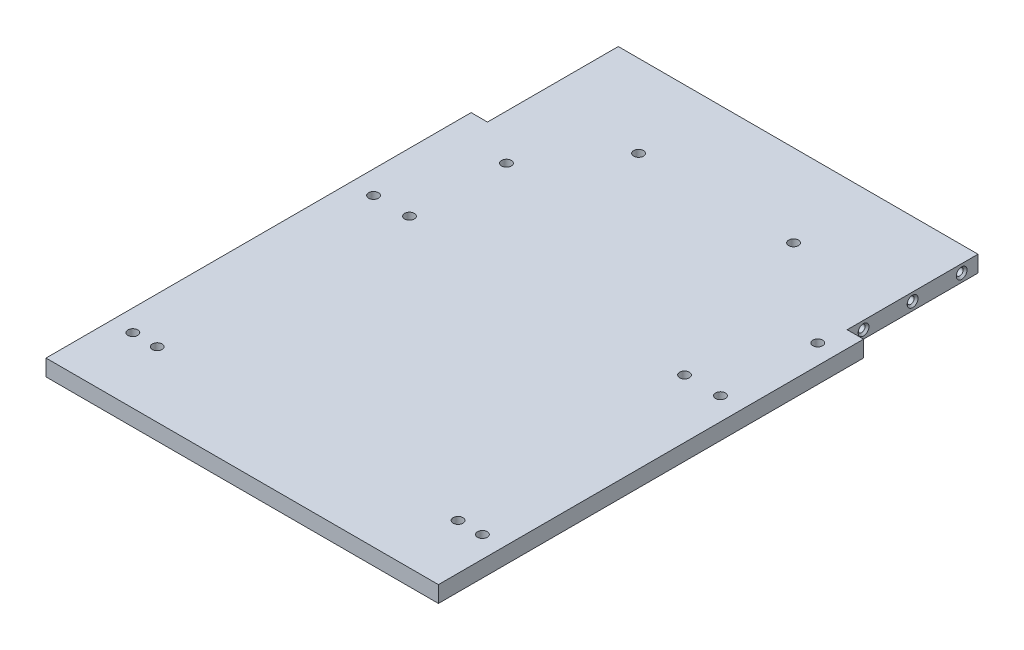
SolidWorks part; units mm, degrees
ref_plane "Front Plane" through (0, 0, 0) normal (0, 0, 1) x (1, 0, 0)
ref_plane "Top Plane" through (0, 0, 0) normal (0, 1, 0) x (1, 0, 0)
ref_plane "Right Plane" through (0, 0, 0) normal (1, 0, 0) x (0, 0, -1)
sketch "Sketch1" plane through (0, 0, 0) normal (0, 1, 0) x (1, 0, 0)
  line L0 (-6.35, 0) -> (-6.35, -50.8)
  line L1 (-6.35, 0) -> (-146.05, 0)
  line L2 (0, -50.8) -> (0, -215.9)
  line L3 (0, -215.9) -> (-152.4, -215.9)
  line L4 (-152.4, -50.8) -> (-152.4, -215.9)
  line L5 (-6.35, -50.8) -> (0, -50.8)
  line L6 (-146.05, 0) -> (-146.05, -50.8)
  line L7 (-146.05, -50.8) -> (-152.4, -50.8)
  point P7 (-3.175, -50.8)
  dimension "D1" = 152.4
  dimension "D2" = 215.9
  dimension "D3" = 50.8
  dimension "D4" = 6.35
  dimension "D5" = 6.35
  dimension "D6" = 50.8
extrude "Boss-Extrude1" add sketch "Sketch1" along normal blind 6.35
sketch "Sketch2" plane through (-6.35, 0, 0) normal (1, 0, 0) x (0, 0, -1)
  line L0 (-50.8, 6.35) -> (-50.8, 0) construction
  line L1 (-50.8, 6.35) -> (-50.8, 0) construction
  line L2 (-50.8, 0) -> (0, 0) construction
  circle A0 centre (-44.45, 3.175) radius 1.8288
  circle A1 centre (-25.4, 3.175) radius 1.8288
  circle A2 centre (-6.35, 3.175) radius 1.8288
  dimension "D4" = 3.175
  dimension "D5" = 3.175
  dimension "D6" = 3.6576
  dimension "D7" = 3.6576
  dimension "D8" = 3.6576
  dimension "D1" = 6.35
  dimension "D2" = 25.4
  dimension "D3" = 44.45
hole_wizard "#6-32 Tapped Hole1" positions "Sketch3" profile "Sketch4" tap size "#6-32" standard "ANSI Inch"
sketch "Sketch3" plane through (-6.35, 0, 0) normal (1, 0, 0) x (0, 0, -1)
  point P0 (-44.45, 3.175)
  point P3 (-25.4, 3.175)
  point P6 (-6.35, 3.175)
sketch "Sketch4" plane through (-6.35, 3.175, 44.45) normal (0, 1, 0) x (0, 0, -1)
  line L0 (0, 0) -> (0, 12.7)
  line L1 (0, 12.7) -> (1.3525, 11.8873)
  line L2 (1.3525, 11.8873) -> (1.3525, 0.748)
  line L3 (1.3525, 0.748) -> (2.1006, 0)
  line L5 (2.1006, 0) -> (0, 0)
  line L6 (-1.3525, 0.748) -> (-2.1006, 0) construction
  line L10 (0, 12.7) -> (-1.3526, 11.8873) construction
  line L11 (0, -6.35) -> (0, 107.95) construction
  dimension "Tap Drill Dia." = 2.7051
  dimension "Tap Drill Depth" = 12.7
  dimension "Near C'Sink Dia." = 4.2012
  dimension "Near C'Sink Angle" = 90
  dimension "Drill Angle" = 118
cosmetic thread "Hole Thread13" parameters "D1"=10.16, "D2"=3.5052
cosmetic thread "Hole Thread14" parameters "D1"=10.16, "D2"=3.5052
cosmetic thread "Hole Thread15" parameters "D1"=10.16, "D2"=3.5052
sketch "Sketch5" plane through (-146.05, 0, 0) normal (-1, 0, 0) x (0, 0, 1)
  circle A0 centre (6.35, 3.175) radius 1.8288
  circle A1 centre (25.4, 3.175) radius 1.8288
  circle A2 centre (44.45, 3.175) radius 1.8288
  dimension "D1" = 3.6576
  dimension "D2" = 3.6576
  dimension "D3" = 3.6576
hole_wizard "#6-32 Tapped Hole2" positions "Sketch6" profile "Sketch7" tap size "#6-32" standard "ANSI Inch"
sketch "Sketch6" plane through (-146.05, 0, 0) normal (-1, 0, 0) x (0, 0, 1)
  point P0 (6.35, 3.175)
  point P3 (25.4, 3.175)
  point P6 (44.45, 3.175)
sketch "Sketch7" plane through (-146.05, 3.175, 6.35) normal (0, 1, 0) x (0, 0, 1)
  line L0 (0, 0) -> (0, 12.7)
  line L1 (0, 12.7) -> (1.3525, 11.8873)
  line L2 (1.3525, 11.8873) -> (1.3525, 0.748)
  line L3 (1.3525, 0.748) -> (2.1006, 0)
  line L5 (2.1006, 0) -> (0, 0)
  line L6 (-1.3525, 0.748) -> (-2.1006, 0) construction
  line L10 (0, 12.7) -> (-1.3526, 11.8873) construction
  line L11 (0, -6.35) -> (0, 107.95) construction
  dimension "Tap Drill Dia." = 2.7051
  dimension "Tap Drill Depth" = 12.7
  dimension "Near C'Sink Dia." = 4.2012
  dimension "Near C'Sink Angle" = 90
  dimension "Drill Angle" = 118
cosmetic thread "Hole Thread16" parameters "D1"=10.16, "D2"=3.5052
cosmetic thread "Hole Thread17" parameters "D1"=10.16, "D2"=3.5052
cosmetic thread "Hole Thread18" parameters "D1"=10.16, "D2"=3.5052
sketch "Sketch9" plane through (0, 6.35, 0) normal (0, 1, 0) x (1, 0, 0)
  line L0 (-152.4, -215.9) -> (0, -215.9) construction
  line L1 (-152.4, -50.8) -> (-152.4, -215.9) construction
  circle A0 centre (-134.62, -190.5) radius 1.8987
  circle A2 centre (-144.0739, -190.5) radius 1.8987
  dimension "D2" = 25.4
  dimension "D3" = 17.78
  dimension "D4" = 3.7973
  dimension "D6" = 3.7973
  dimension "D7" = 9.4539
  dimension "D8" = 25.4
sketch "Sketch16" plane through (0, 6.35, 0) normal (0, 1, 0) x (1, 0, 0)
  line L0 (-6.35, -50.8) -> (-6.35, 0) construction
  line L1 (-6.35, 0) -> (-146.05, 0) construction
  circle A0 centre (-45.974, -32.004) radius 1.8986
  circle A1 centre (-106.172, -32.004) radius 1.8987
  dimension "D1" = 39.624
  dimension "D2" = 32.004
  dimension "D3" = 60.198
  dimension "D4" = 32.004
  dimension "D5" = 3.7973
  dimension "D6" = 3.7973
sketch "Sketch20" plane through (0, 6.35, 0) normal (0, 1, 0) x (1, 0, 0)
  line L0 (0, -50.8) -> (-6.35, -50.8) construction
  line L1 (0, -215.9) -> (0, -50.8) construction
  line L2 (-146.05, -50.8) -> (-152.4, -50.8) construction
  line L4 (-152.4, -50.8) -> (-152.4, -215.9) construction
  circle A0 centre (-128.524, -60.96) radius 1.8987
  circle A1 centre (-129.54, -97.5981) radius 1.8987
  circle A2 centre (-143.4846, -97.6122) radius 1.8987
  circle A3 centre (-7.62, -60.96) radius 1.8987
  circle A4 centre (-22.7076, -97.6122) radius 1.8986
  circle A5 centre (-8.763, -97.6122) radius 1.8987
  dimension "D1" = 10.16
  dimension "D2" = 7.62
  dimension "D3" = 36.6522
  dimension "D4" = 8.763
  dimension "D5" = 13.9446
  dimension "D6" = 36.6522
  dimension "D7" = 3.7973
  dimension "D8" = 3.7973
  dimension "D9" = 3.7973
  dimension "D10" = 3.7973
  dimension "D11" = 3.7973
  dimension "D12" = 3.7973
  dimension "D13" = 10.16
  dimension "D14" = 36.6522
  dimension "D15" = 13.9446
  dimension "D16" = 36.6522
  dimension "D17" = 23.876
  dimension "D18" = 22.86
sketch "Sketch25" plane through (0, 6.35, 0) normal (0, 1, 0) x (1, 0, 0)
  line L0 (-152.4, -215.9) -> (0, -215.9) construction
  circle A0 centre (-8.3261, -190.5) radius 1.8987
  circle A3 centre (-17.78, -190.5) radius 1.8987
  dimension "D1" = 3.7973
  dimension "D2" = 9.4539
  dimension "D3" = 25.4
  dimension "D4" = 3.7973
extrude "Cut-Extrude1" cut sketch "Sketch25" against normal through all
extrude "Cut-Extrude2" cut sketch "Sketch20" against normal through all
extrude "Cut-Extrude3" cut sketch "Sketch16" against normal through all
extrude "Cut-Extrude4" cut sketch "Sketch9" against normal through all
